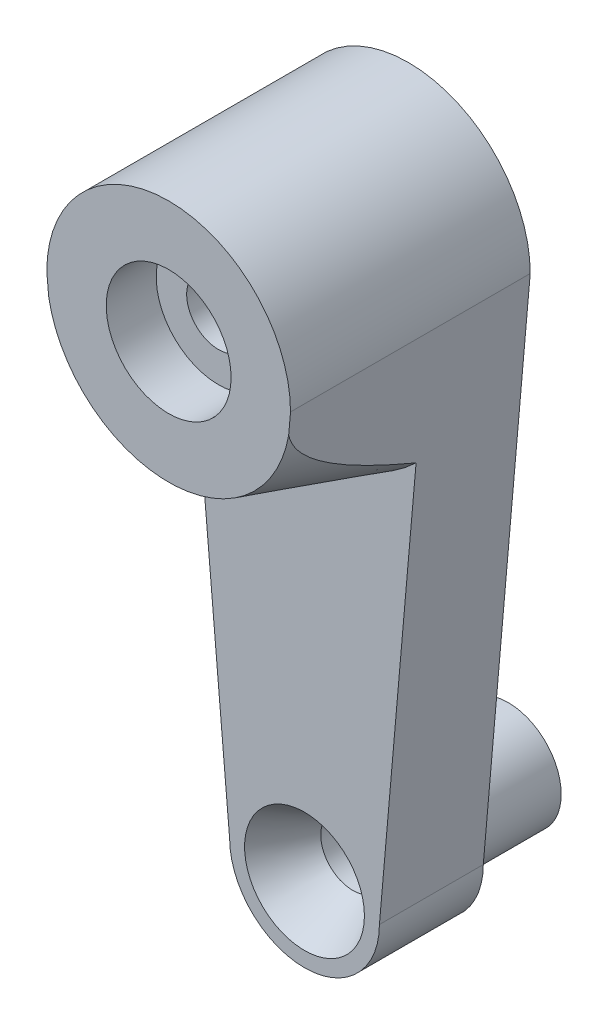
SolidWorks part; units mm, degrees
ref_plane "前视基准面" through (0, 0, 0) normal (0, 0, 1) x (1, 0, 0)
ref_plane "上视基准面" through (0, 0, 0) normal (0, 1, 0) x (1, 0, 0)
ref_plane "右视基准面" through (0, 0, 0) normal (1, 0, 0) x (0, 0, -1)
sketch "草图1" plane through (0, 0, 0) normal (0, 0, 1) x (1, 0, 0)
  line L0 (-3.75, -26.8) -> (-6.1, 0)
  line L1 (6.1, 0) -> (3.75, -26.8)
  arc A0 (6.1, 0) -> (-6.1, 0) centre (0, 0) ccw
  arc A1 (-3.75, -26.8) -> (3.75, -26.8) centre (0, -26.8) ccw
  circle A2 centre (0, 0) radius 1.6
  circle A3 centre (0, -26.8) radius 1.6
  dimension "D1" = 3.2
  dimension "D2" = 26.8
extrude "凸台-拉伸1" add sketch "草图1" along normal blind 12
sketch "草图3" plane through (0, 0, 12) normal (0, 0, 1) x (1, 0, 0)
  line L0 (-6.0069, -1.0616) -> (-3.75, -26.8)
  line L1 (3.75, -26.8) -> (6.0069, -1.0616)
  arc A0 (-6.0069, -1.0616) -> (6.0069, -1.0616) centre (0, 0) ccw
  arc A1 (-3.75, -26.8) -> (3.75, -26.8) centre (0, -26.8) ccw
extrude "切除-拉伸1" cut sketch "草图3" against normal blind 6.8
sketch "草图4" plane through (0, 0, 0) normal (0, 0, -1) x (-1, 0, 0)
  circle A0 centre (0, 0) radius 3.125
  dimension "D1" = 6.25
sketch "草图5" plane through (0, 0, 0) normal (0, 0, -1) x (-1, 0, 0)
  circle A0 centre (0, -26.8) radius 2.65
  circle A1 centre (0, -26.8) radius 1.55
  dimension "D1" = 5.3
  dimension "D2" = 3.1
extrude "凸台-拉伸2" add sketch "草图5" along normal blind 5
chamfer "倒角1" distance 0.5 distance2 0.5 1 edges at (2.65, -26.8, 0)
sketch "草图6" plane through (0, 0, 12) normal (0, 0, 1) x (1, 0, 0)
  circle A0 centre (0, 0) radius 1.6
  circle A1 centre (0, 0) radius 3.125
  dimension "D1" = 6.25
chamfer "倒角2" distance 6.8 distance2 2 1 edges at (0, -6.1, 5.2) first distance on face at (0, -3.5808, 8.6)
extrude "切除-拉伸2" cut sketch "草图4" against normal blind 2.5
extrude "切除-拉伸3" cut sketch "草图6" against normal blind 2.5
ref_plane "基准面1" through (0, -26.8, 0) normal (0, 1, 0) x (1, 0, 0)
sketch "草图7" plane through (0, -26.8, 0) normal (0, 1, 0) x (1, 0, 0)
  line L0 (0, -2.7) -> (1.55, -2.7)
  line L1 (1.55, -2.7) -> (3, -5.2)
  line L2 (3, -5.2) -> (0, -5.2)
  line L3 (0, -5.2) -> (0, -2.7)
  line L4 (0, -10.6437) -> (0, 1.286) construction
  line L5 (-3.75, -5.2) -> (3.75, -5.2) construction
  point P8 (0, -2.7)
  point P9 (3, -5.2)
  dimension "D1" = 3
  dimension "D2" = 2.5
revolve "切除-旋转1" cut sketch "草图7" angle 360 about L3
